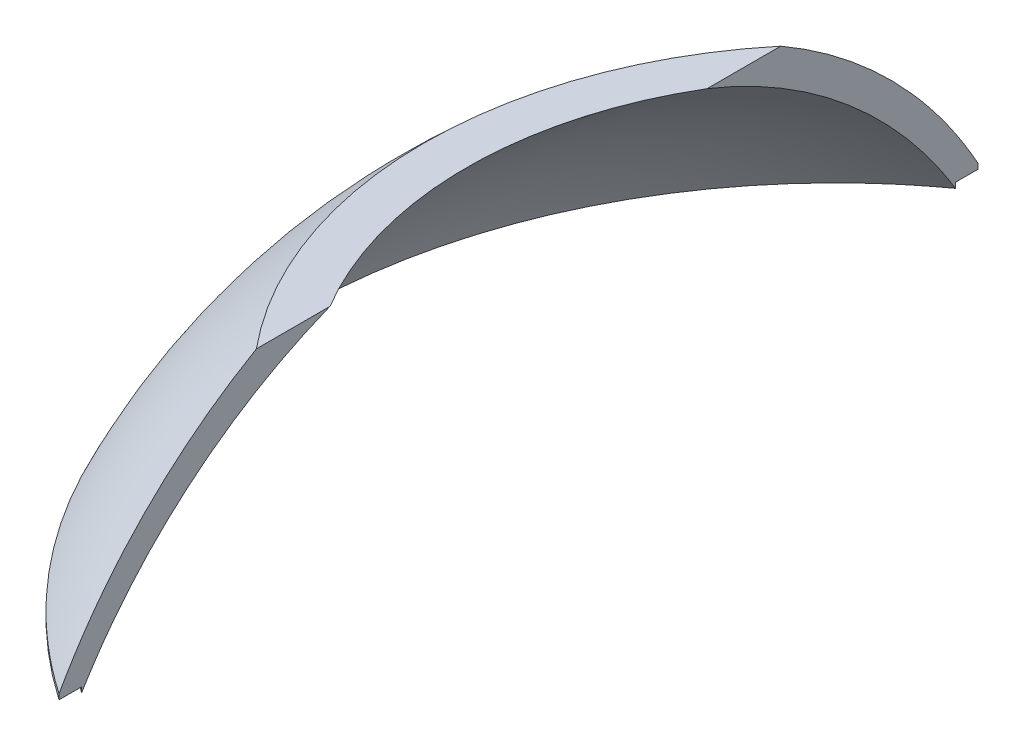
SolidWorks part; units mm, degrees
ref_plane "Front Plane" through (0, 0, 0) normal (0, 0, 1) x (1, 0, 0)
ref_plane "Top Plane" through (0, 0, 0) normal (0, 1, 0) x (1, 0, 0)
ref_plane "Right Plane" through (0, 0, 0) normal (1, 0, 0) x (0, 0, -1)
sketch "Sketch1" plane through (0, 0, 0) normal (0, 1, 0) x (1, 0, 0)
  circle A0 centre (0, 0) radius 106
  dimension "D1" = 212
extrude "Boss-Extrude1" add sketch "Sketch1" along normal blind 1
dome "Dome1" faces to dome 1 distance 68 reverse direction no elliptical dome no face at (0, 1, 106) parameters "D1"=68
sketch "Sketch3" plane through (0, 0, 0) normal (0, -1, 0) x (1, 0, 0)
  circle A0 centre (0, 0) radius 102.5
extrude "Boss-Extrude2" add sketch "Sketch3" along normal blind 1
dome "Dome3" faces to dome 1 distance 64 reverse direction yes elliptical dome no face at (0, -1, -102.5) parameters "D1"=64
ref_plane "Plane2" through (0, 69, 0) normal (0, 1, 0) x (1, 0, 0)
sketch "Sketch4" plane through (0, 69, 0) normal (0, 1, 0) x (1, 0, 0)
  circle A0 centre (0, 0) radius 141.4952
extrude "Cut-Extrude1" cut sketch "Sketch4" against normal blind 30
sketch "Sketch6" plane through (0, 39, 0) normal (0, 1, 0) x (1, 0, 0)
  line L1 (-60.1392, 135.5362) -> (116.9228, 135.5362)
  line L2 (-60.1392, 135.5362) -> (-60.1392, -131.1785)
  line L3 (-60.1392, -131.1785) -> (116.9228, -131.1785)
  line L4 (116.9228, 135.5362) -> (116.9228, -131.1785)
extrude "Cut-Extrude3" cut sketch "Sketch6" against normal blind 61
